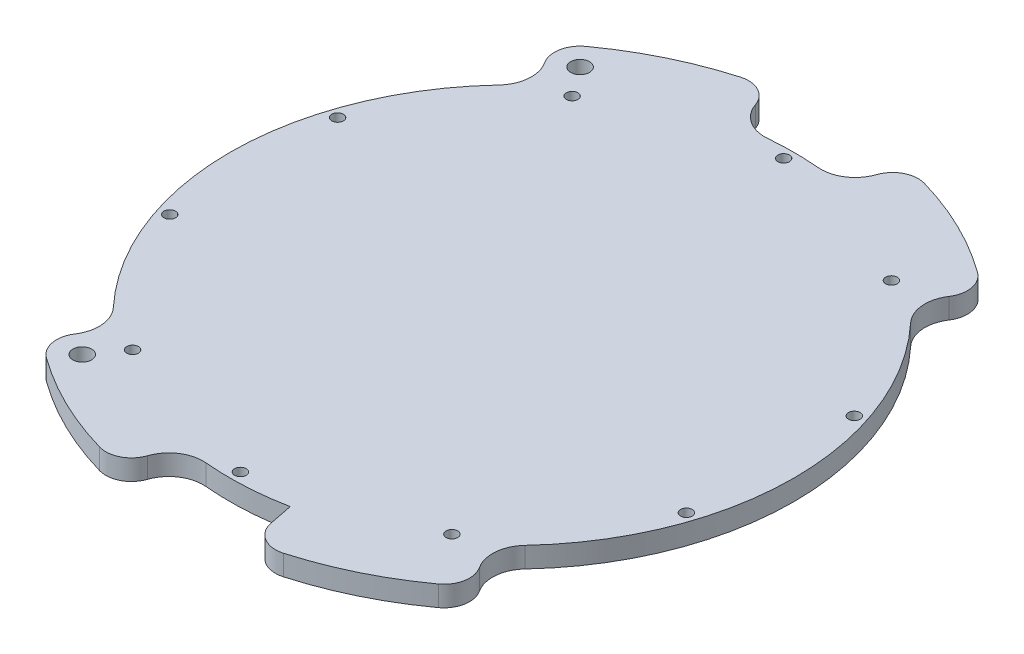
SolidWorks part; units mm, degrees
material "Acrylic (Medium-high impact)"
ref_plane "Front Plane" through (0, 0, 0) normal (0, 0, 1) x (1, 0, 0)
ref_plane "Top Plane" through (0, 0, 0) normal (0, 1, 0) x (1, 0, 0)
ref_plane "Right Plane" through (0, 0, 0) normal (1, 0, 0) x (0, 0, -1)
sketch "Sketch1" plane through (0, 0, 0) normal (0, 1, 0) x (1, 0, 0)
  line L0 (0, 0) -> (0, 79.5) construction
  line L1 (0, 0) -> (46.7289, 64.3169) construction
  line L4 (0, 0) -> (-52.9347, 72.8584) construction
  line L5 (-1000, 0) -> (49000, 0) construction
  line L7 (-58.6141, 67.96) -> (0, 0) construction
  line L9 (-58.6141, -67.96) -> (0, 0) construction
  line L11 (-58.6141, 67.96) -> (-53.9149, 62.5115)
  line L12 (-58.6141, -67.96) -> (-53.9149, -62.5115)
  line L14 (-52.9347, 72.8584) -> (-57.3431, 78.926) construction
  line L15 (0, 0) -> (-26.8906, 93.7786) construction
  line L16 (-42.7666, 87.6844) -> (0, 0) construction
  line L17 (-17.4667, 88.0289) -> (-16.0664, 80.9714)
  line L18 (-17.4667, -88.0289) -> (-16.0664, -80.9714)
  line L19 (17.4667, -88.0289) -> (16.0664, -80.9714)
  line L20 (58.6141, -67.96) -> (53.9149, -62.5115)
  line L21 (58.6141, 67.96) -> (53.9149, 62.5115)
  line L22 (17.4667, 88.0289) -> (16.0664, 80.9714)
  arc A0 (0, 79.5) -> (-51.9229, -60.2019) centre (0, 0) ccw construction
  arc A1 (-53.9149, 62.5115) -> (-53.9149, -62.5115) centre (0, 0) ccw
  circle A3 centre (-52.9347, 72.8584) radius 2.75
  arc A4 (-58.6141, 67.96) -> (-57.3431, 78.926) centre (-52.9347, 72.8584) cw
  arc A5 (-58.6141, -67.96) -> (-57.3431, -78.926) centre (-52.9347, -72.8584) ccw
  arc A6 (-16.0664, -80.9714) -> (16.0664, -80.9714) centre (0, 0) ccw
  circle A7 centre (-52.9347, -72.8584) radius 2.75
  arc A8 (-57.3431, 78.926) -> (-26.8906, 93.7786) centre (0, 0) cw
  arc A9 (-17.4667, 88.0289) -> (-26.8906, 93.7786) centre (-24.8233, 86.5692) ccw
  arc A10 (-17.4667, -88.0289) -> (-26.8906, -93.7786) centre (-24.8233, -86.5692) cw
  arc A11 (-57.3431, -78.926) -> (-26.8906, -93.7786) centre (0, 0) ccw
  arc A12 (17.4667, -88.0289) -> (26.8906, -93.7786) centre (24.8233, -86.5692) ccw
  arc A13 (57.3431, -78.926) -> (26.8906, -93.7786) centre (0, 0) cw
  arc A14 (58.6141, -67.96) -> (57.3431, -78.926) centre (52.9347, -72.8584) cw
  arc A15 (58.6141, 67.96) -> (57.3431, 78.926) centre (52.9347, 72.8584) ccw
  arc A16 (57.3431, 78.926) -> (26.8906, 93.7786) centre (0, 0) ccw
  arc A17 (17.4667, 88.0289) -> (26.8906, 93.7786) centre (24.8233, 86.5692) cw
  arc A18 (16.0664, 80.9714) -> (-16.0664, 80.9714) centre (0, 0) ccw
  arc A19 (79.5, 0) -> (46.7289, 64.3169) centre (0, 0) ccw construction
  arc A20 (53.9149, -62.5115) -> (53.9149, 62.5115) centre (0, 0) ccw
  point P4 (0, 79.5)
  point P5 (46.7289, 64.3169)
  point P8 (75.609, 24.5669)
  point P9 (75.609, -24.5669)
  point P10 (46.7289, -64.3169)
  point P11 (0, -79.5)
  point P12 (-46.7289, -64.3169)
  point P13 (-75.609, -24.5669)
  point P14 (-75.609, 24.5669)
  point P15 (-46.7289, 64.3169)
  point P16 (0, 0)
  point P28 (-23.0888, 79.5)
  point P33 (-45.1478, 86.4824)
  point P34 (0, 0)
  point P37 (0, 0)
  dimension "D1" = 159
  dimension "D2" = 165.1
  dimension "D5" = 7.5
  dimension "D6" = 5.5
  dimension "D7" = 20
  dimension "D8" = 97.5579
  dimension "D4" = 36
  dimension "D3" = 10
extrude "Boss-Extrude1" add sketch "Sketch1" along normal mid plane 6
hole_wizard "M3 Clearance Hole1" positions "Sketch2" profile "Sketch3" hole size "M3" standard "ANSI Metric" end condition through all
sketch "Sketch2" plane through (0, 3, 0) normal (0, 1, 0) x (1, 0, 0)
  point P0 (0, 79.5)
  point P3 (46.7289, 64.3169)
  point P6 (75.609, 24.5669)
  point P9 (75.609, -24.5669)
  point P12 (46.7289, -64.3169)
  point P15 (0, -79.5)
  point P18 (-46.7289, -64.3169)
  point P21 (-75.609, -24.5669)
  point P24 (-75.609, 24.5669)
  point P27 (-46.7289, 64.3169)
sketch "Sketch3" plane through (0, 3, -79.5) normal (1, 0, 0) x (0, 0, 1)
  line L0 (0, 0) -> (0, 6)
  line L1 (0, 6) -> (1.7, 6)
  line L2 (1.7, 6) -> (1.7, 0)
  line L5 (1.7, 0) -> (0, 0)
  line L11 (0, -6.35) -> (0, 107.95) construction
  dimension "Thru Hole Dia." = 3.4
  dimension "Thru Hole Depth" = 6
fillet "Fillet2" radius 10 7 edges at (-53.9149, 0, 62.5115) (-53.9149, 0, -62.5115) (-16.0664, 0, 80.9714) (53.9149, 0, 62.5115) (53.9149, 0, -62.5115) (16.0664, 0, -80.9714) (-16.0664, 0, -80.9714)
